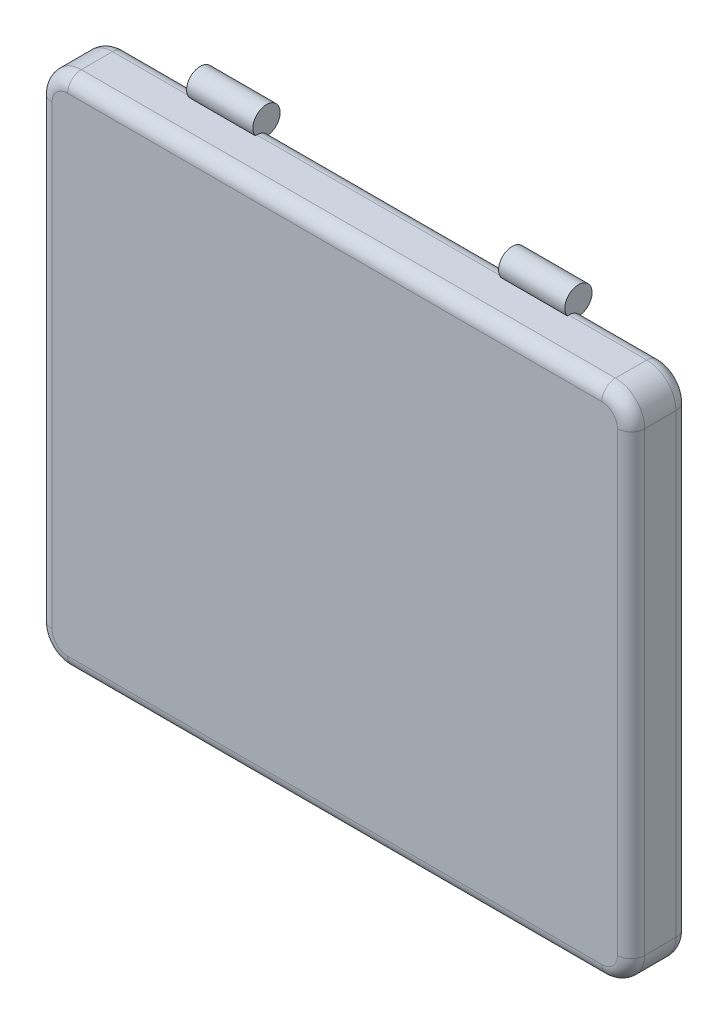
SolidWorks part; units mm, degrees
material "ABS PC"
ref_plane "Front Plane" through (0, 0, 0) normal (0, 0, 1) x (1, 0, 0)
ref_plane "Top Plane" through (0, 0, 0) normal (0, 1, 0) x (1, 0, 0)
ref_plane "Right Plane" through (0, 0, 0) normal (1, 0, 0) x (0, 0, -1)
sketch "Block sketch 1" plane through (0, 0, 0) normal (0, 0, 1) x (1, 0, 0)
  line L0 (358, -132) -> (632, -132)
  line L1 (647, -117) -> (647, 117)
  line L2 (632, 132) -> (358, 132)
  line L3 (343, 117) -> (343, -117)
  arc A0 (632, -132) -> (647, -117) centre (632, -117) ccw
  arc A1 (647, 117) -> (632, 132) centre (632, 117) ccw
  arc A2 (358, 132) -> (343, 117) centre (358, 117) ccw
  arc A3 (343, -117) -> (358, -132) centre (358, -117) ccw
  dimension "D1" = 15
  dimension "D2" = 304
  dimension "D3" = 264
extrude "Block 1" add sketch "Block sketch 1" along normal blind 30 from offset 465 separate body
fillet "Block edge fillet 1" radius 7 16 edges at (347.3934, -127.6066, 495) (347.3934, 127.6066, 495) (642.6066, 127.6066, 495) (642.6066, -127.6066, 495) (642.6066, 127.6066, 465) (642.6066, -127.6066, 465) (495, -132, 465) (347.3934, -127.6066, 465) (343, 0, 465) (347.3934, 127.6066, 465) (647, 0, 495) (343, 0, 495) (495, 132, 495) (495, -132, 495) (647, 0, 465) (495, 132, 465)
sketch "Extrude sketch 1" plane through (0, 0, 0) normal (0, 0, 1) x (1, 0, 0)
  circle A0 centre (0, 0) radius 7
  dimension "D1" = 14
extrude "Extrude 1" add sketch "Extrude sketch 1" along normal blind 34 from offset 17 separate body offset against normal yes
move or copy body "Extrude rotate 1" bodies to move or copy 102 copy no rotation origin (0, 0, 0) rotation axis (0, 1, 0) rotation angle 90
move or copy body "Extrude place 1" bodies to move or copy 103 copy no translate (415, 136, 467) parameters "D1"=415, "D2"=136, "D3"=467
sketch "Extrude sketch 2" plane through (0, 0, 0) normal (0, 0, 1) x (1, 0, 0)
  circle A0 centre (0, 0) radius 7
  dimension "D1" = 14
extrude "Extrude 2" add sketch "Extrude sketch 2" along normal blind 34 from offset 17 separate body offset against normal yes
move or copy body "Extrude rotate 2" bodies to move or copy 105 copy no rotation origin (0, 0, 0) rotation axis (0, 1, 0) rotation angle 90
move or copy body "Extrude place 2" bodies to move or copy 106 copy no translate (575, 136, 467) parameters "D1"=575, "D2"=136, "D3"=467
combine bodies "Combine (weld / assembly of features)" operation type add bodies to combine 101 107 104
